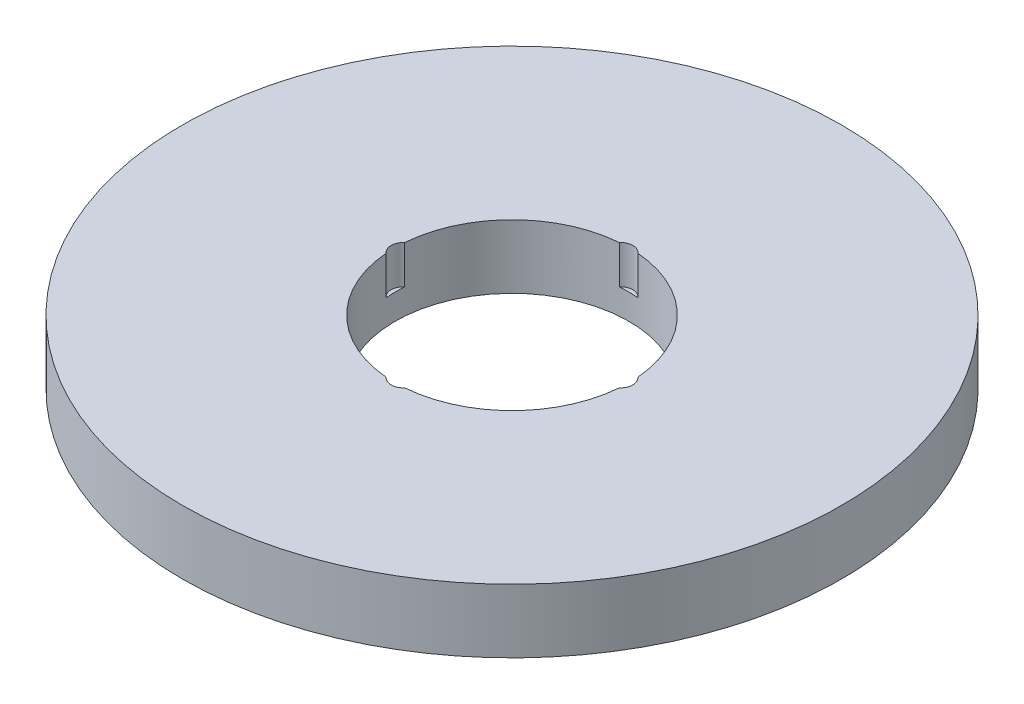
SolidWorks part; units mm, degrees
ref_plane "Front Plane" through (0, 0, 0) normal (0, 0, 1) x (1, 0, 0)
ref_plane "Top Plane" through (0, 0, 0) normal (0, 1, 0) x (1, 0, 0)
ref_plane "Right Plane" through (0, 0, 0) normal (1, 0, 0) x (0, 0, -1)
sketch "Sketch1" plane through (0, 0, 0) normal (0, 1, 0) x (1, 0, 0)
  circle A0 centre (0, 0) radius 77.5
  dimension "FLANGE_OD" = 155
extrude "Boss-Extrude1" add sketch "Sketch1" along normal blind 15
sketch "Sketch2" plane through (0, 0, 0) normal (0, 1, 0) x (1, 0, 0)
  circle A0 centre (0, 0) radius 27.5
  dimension "BORE_D" = 55
extrude "Cut-Extrude1" cut sketch "Sketch2" along normal through all
sketch "Sketch3" plane through (0, 15, 0) normal (0, 1, 0) x (1, 0, 0)
  circle A0 centre (0, 0) radius 25.5393 construction
  circle A1 centre (-25.5393, 0) radius 2.8792
  dimension "BOLT_D" = 5.7584
  dimension "BOLT_PCD" = 51.0786
extrude "Cut-Extrude2" cut sketch "Sketch3" against normal blind 9.0395
pattern_circular "CirPattern1" count 4 over 360 about axis through (0, 0, 0) along (0, 1, 0) of "Cut-Extrude2"
